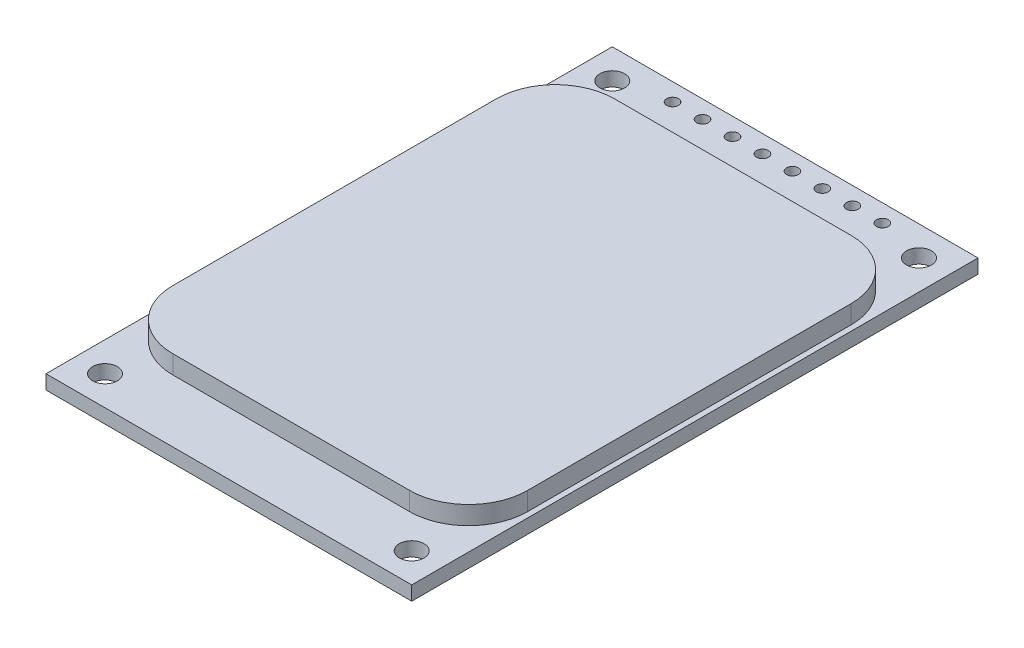
SolidWorks part; units mm, degrees
ref_plane "前视基准面" through (0, 0, 0) normal (0, 0, 1) x (1, 0, 0)
ref_plane "上视基准面" through (0, 0, 0) normal (0, 1, 0) x (1, 0, 0)
ref_plane "右视基准面" through (0, 0, 0) normal (1, 0, 0) x (0, 0, -1)
other "Configuration Table"
sketch "草图1" plane through (0, 0, 0) normal (0, 1, 0) x (1, 0, 0)
  line L1 (0, 0) -> (31, 0)
  line L2 (0, 0) -> (0, -48)
  line L3 (0, -48) -> (31, -48)
  line L4 (31, 0) -> (31, -48)
  dimension "D1" = 31
  dimension "D2" = 48
extrude "凸台-拉伸1" add sketch "草图1" along normal blind 1.2
sketch "草图2" plane through (0, 1.2, 0) normal (0, 1, 0) x (1, 0, 0)
  line L0 (15.5, 0) -> (15.5, -48) construction
  line L1 (31, 0) -> (0, 0) construction
  line L2 (0, -48) -> (31, -48) construction
  line L3 (0, -24) -> (31, -24) construction
  line L4 (0, 0) -> (0, -48) construction
  line L5 (31, -48) -> (31, 0) construction
  circle A0 centre (2.5, -2.5) radius 1.05
  circle A1 centre (28.5, -2.5) radius 1.05
  circle A2 centre (2.5, -45.5) radius 1.05
  circle A3 centre (28.5, -45.5) radius 1.05
  dimension "D1" = 26
  dimension "D2" = 43
  dimension "D3" = 2.1
extrude "切除-拉伸1" cut sketch "草图2" against normal up to next
sketch "草图3" plane through (0, 1.2, 0) normal (0, 1, 0) x (1, 0, 0)
  line L0 (15.5, 0) -> (15.5, -48) construction
  line L1 (31, 0) -> (0, 0) construction
  line L2 (0, -48) -> (31, -48) construction
  circle A0 centre (14.23, -1.5) radius 0.5
  circle A1 centre (2.5, -2.5) radius 1.05 construction
  circle A2 centre (11.69, -1.5) radius 0.5
  circle A3 centre (9.15, -1.5) radius 0.5
  circle A4 centre (6.61, -1.5) radius 0.5
  circle A5 centre (24.39, -1.5) radius 0.5
  circle A6 centre (21.85, -1.5) radius 0.5
  circle A7 centre (19.31, -1.5) radius 0.5
  circle A8 centre (16.77, -1.5) radius 0.5
  dimension "D1" = 1
  dimension "D2" = 1.27
  dimension "D3" = 1
  dimension "D5" = 2.54
  dimension "D4" = 4
extrude "切除-拉伸2" cut sketch "草图3" against normal up to next
sketch "草图4" plane through (0, 1.2, 0) normal (0, 1, 0) x (1, 0, 0)
  line L0 (0, -24) -> (31, -24) construction
  line L1 (0.465, -5.285) -> (30.535, -5.285)
  line L2 (0.465, -5.285) -> (0.465, -42.715)
  line L3 (0.465, -42.715) -> (30.535, -42.715)
  line L4 (30.535, -5.285) -> (30.535, -42.715)
  line L5 (0, 0) -> (0, -48) construction
  line L6 (31, -48) -> (31, 0) construction
  line L7 (15.5, 0) -> (15.5, -48) construction
  line L8 (31, 0) -> (0, 0) construction
  line L9 (0, -48) -> (31, -48) construction
  dimension "D1" = 30.07
  dimension "D2" = 37.43
extrude "凸台-拉伸2" add sketch "草图4" along normal blind 1.56
fillet "圆角1" radius 5 4 edges at (0.465, 1.98, 42.715) (30.535, 1.98, 42.715) (30.535, 1.98, 5.285) (0.465, 1.98, 5.285)
